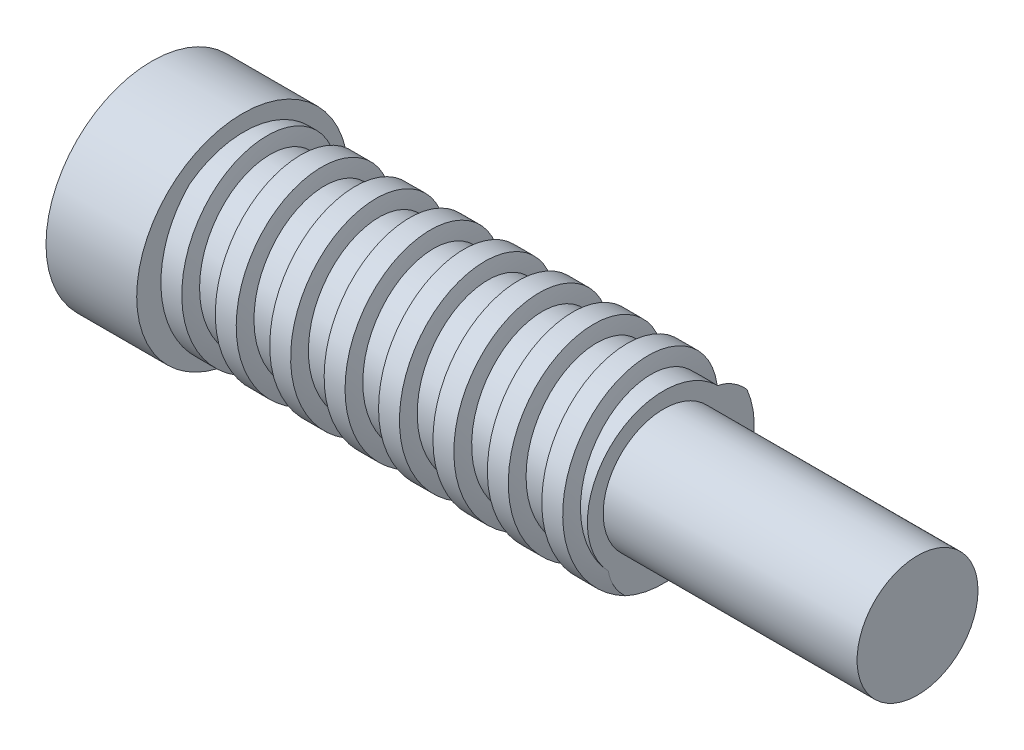
SolidWorks part; units mm, degrees
ref_plane "Piano frontale" through (0, 0, 0) normal (0, 0, 1) x (1, 0, 0)
ref_plane "Piano superiore" through (0, 0, 0) normal (0, 1, 0) x (1, 0, 0)
ref_plane "Piano destro" through (0, 0, 0) normal (1, 0, 0) x (0, 0, -1)
sketch "Schizzo1" plane through (0, 0, 0) normal (0, 0, 1) x (1, 0, 0)
  line L1 (3.0478, 1.2286) -> (21.0478, 1.2286)
  line L2 (3.0478, 1.2286) -> (3.0478, 4.2286)
  line L3 (3.0478, 4.2286) -> (21.0478, 4.2286)
  line L4 (21.0478, 1.2286) -> (21.0478, 4.2286)
  dimension "D1" = 18
  dimension "D2" = 3
revolve "Rivoluzione1" add sketch "Schizzo1" angle 360 about L1
sketch "Schizzo2" plane through (0, 0, 0) normal (0, 0, 1) x (1, 0, 0)
  line L0 (-3.0902, -11.7478) -> (-3.0902, 4.2522) construction
  line L1 (-2.5318, 4.2425) -> (1.2761, 3.1245) construction
  line L2 (-4.1212, 5.2754) -> (-2.0591, 5.2754)
  line L3 (-3.0902, -11.7478) -> (-2.5318, 4.2425) construction
  arc A2 (-2.6436, 3.7458) -> (-3.5368, 3.7458) centre (-3.0902, -11.7478) ccw
  arc A3 (-2.0591, 5.2754) -> (-2.6436, 3.7458) centre (1.2761, 3.1245) ccw
  arc A6 (-4.1212, 5.2754) -> (-3.5368, 3.7458) centre (-7.4565, 3.1245) cw
  dimension "D1" = 31
  dimension "D4" = 2
ref_plane "Piano1" through (24.0478, 0, 0) normal (1, 0, 0) x (0, 0, -1)
sketch "Schizzo3" plane through (24.0478, 0, 0) normal (1, 0, 0) x (0, 0, -1)
  circle A0 centre (0, 1.2286) radius 3 construction
  circle A1 centre (0, 1.2286) radius 3
curve "Elica/Spirale1" pitch 1.8 height 36 radius 3 centre (24.0478, 1.2286, 0) axis (-1, 0, 0) start towards (0, 0, 1)
sweep "Taglia-Sweep2" cut profiles "Schizzo2" path "Elica/Spirale1" align with end faces yes
sketch "Schizzo4" plane through (0, 0, 0) normal (0, 0, 1) x (1, 0, 0)
  line L0 (16.9301, 6.4536) -> (16.9301, -3.1913)
  line L1 (16.9301, -3.1913) -> (25.1287, -3.1913)
  line L2 (25.1287, -3.1913) -> (25.1287, 6.4536)
  line L3 (25.1287, 6.4536) -> (16.9301, 6.4536)
extrude "Taglio-Estrusione1" cut sketch "Schizzo4" along normal through all both and the other way through all
sketch "Schizzo5" plane through (0, 0, 0) normal (1, 0, 0) x (0, 0, -1)
  circle A0 centre (0, 1.2286) radius 3.5
  dimension "D1" = 7
extrude "Estrusione-Estrusione1" add sketch "Schizzo5" along normal blind 3 separate body
sketch "Schizzo6" plane through (0, 0, 0) normal (-1, 0, 0) x (0, 0, 1)
  line L1 (0, 2.7286) -> (-1.299, 1.9786)
  line L2 (-1.299, 1.9786) -> (-1.299, 0.4786)
  line L3 (-1.299, 0.4786) -> (0, -0.2714)
  line L4 (0, -0.2714) -> (1.299, 0.4786)
  line L5 (1.299, 0.4786) -> (1.299, 1.9786)
  line L6 (1.299, 1.9786) -> (0, 2.7286)
  circle A0 centre (0, 1.2286) radius 1.299 construction
  dimension "D1" = 1.5
extrude "Taglio-Estrusione2" cut sketch "Schizzo6" against normal blind 5
sketch "Schizzo7" plane through (16.9301, 0, 0) normal (1, 0, 0) x (0, 0, -1)
  circle A0 centre (0, 1.2286) radius 2
  dimension "D1" = 4
extrude "Estrusione-Estrusione2" add sketch "Schizzo7" along normal blind 8.4
